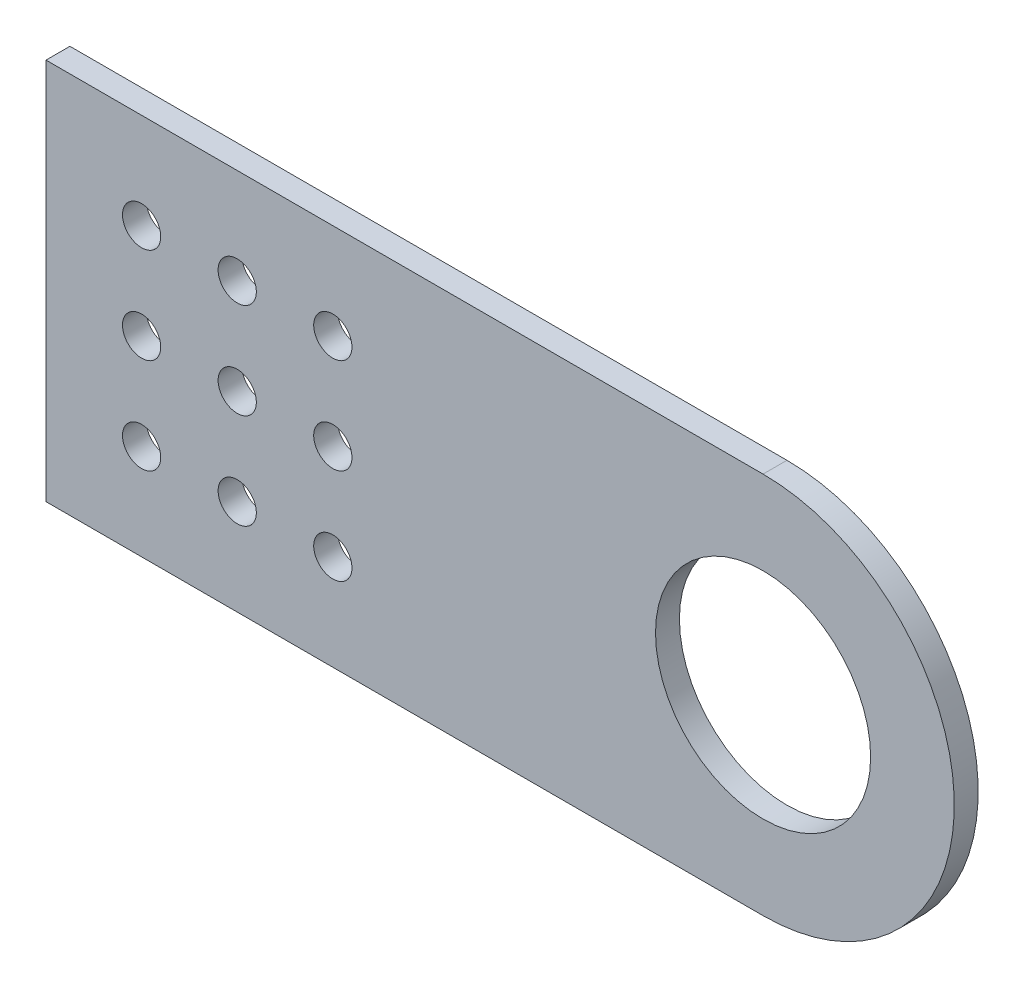
SolidWorks part; units mm, degrees
ref_plane "Front Plane" through (0, 0, 0) normal (0, 0, 1) x (1, 0, 0)
ref_plane "Top Plane" through (0, 0, 0) normal (0, 1, 0) x (1, 0, 0)
ref_plane "Right Plane" through (0, 0, 0) normal (1, 0, 0) x (0, 0, -1)
sketch "Sketch1" plane through (0, 0, 0) normal (0, 0, 1) x (1, 0, 0)
  line L0 (0, 0) -> (0, 50.8)
  line L1 (0, 50.8) -> (95.25, 50.8)
  line L2 (95.25, 0) -> (0, 0)
  arc A0 (95.25, 50.8) -> (95.25, 0) centre (95.25, 25.4) cw
  circle A1 centre (12.7, 38.1) radius 2.54
  circle A2 centre (25.4, 38.1) radius 2.54
  circle A3 centre (38.1, 38.1) radius 2.54
  circle A4 centre (25.4, 25.4) radius 2.54
  circle A5 centre (38.1, 25.4) radius 2.54
  circle A6 centre (25.4, 12.7) radius 2.54
  circle A7 centre (38.1, 12.7) radius 2.54
  circle A8 centre (12.7, 25.4) radius 2.54
  circle A9 centre (12.7, 12.7) radius 2.54
  circle A10 centre (95.25, 25.4) radius 14.2875
  dimension "D3" = 5.08
  dimension "D10" = 28.575
  dimension "D1" = 50.8
  dimension "D2" = 95.25
  dimension "D4" = 12.7
  dimension "D5" = 12.7
  dimension "D8" = 12.7
  dimension "D9" = 12.7
  dimension "D6" = 3
  dimension "D7" = 3
extrude "Boss-Extrude1" add sketch "Sketch1" along normal blind 3.175
